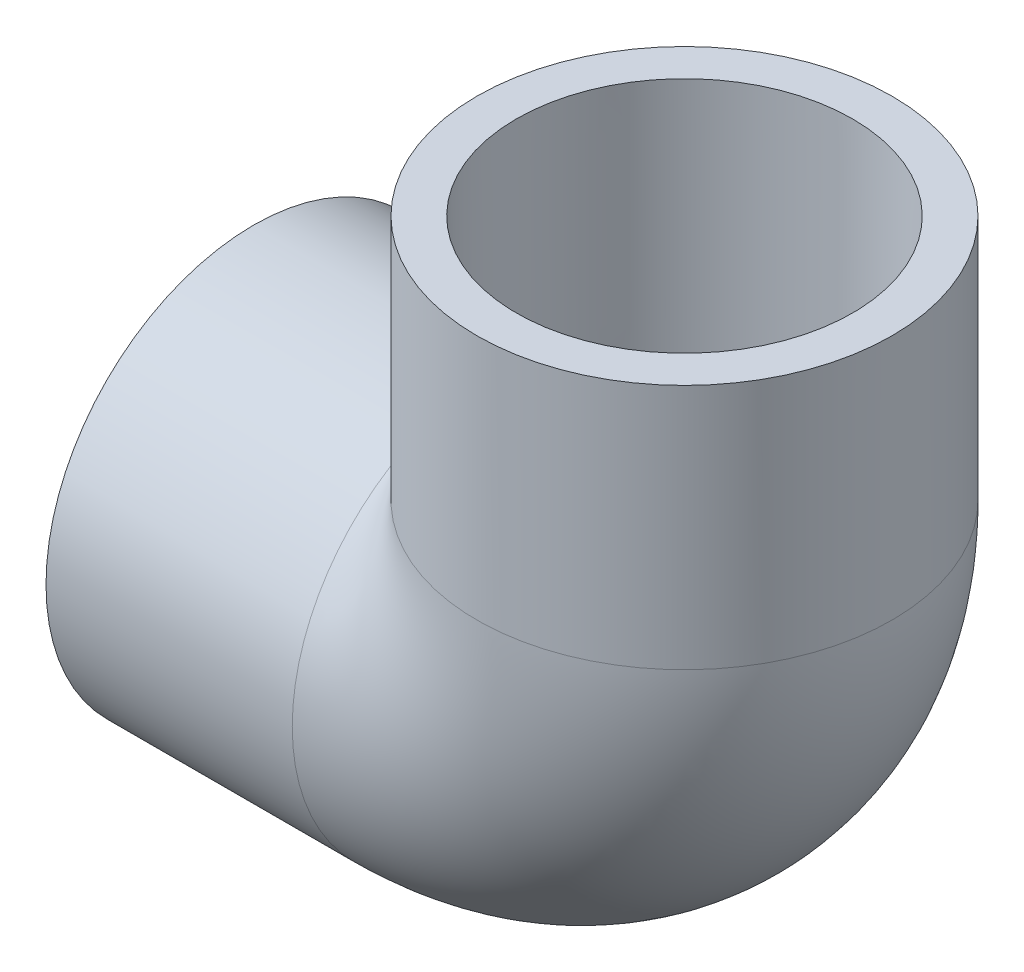
SolidWorks part; units mm, degrees
ref_plane "Front Plane" through (0, 0, 0) normal (0, 0, 1) x (1, 0, 0)
ref_plane "Top Plane" through (0, 0, 0) normal (0, 1, 0) x (1, 0, 0)
ref_plane "Right Plane" through (0, 0, 0) normal (1, 0, 0) x (0, 0, -1)
sketch "Sketch0" plane through (0, 0, 0) normal (0, 0, 1) x (1, 0, 0)
  line L0 (-62.23, 0) -> (0, 0) construction
  line L1 (0, 0) -> (0, 62.23) construction
  line L2 (-26.67, 0) -> (0, 0) construction
  line L3 (0, 0) -> (0, 26.67) construction
  line L4 (-62.23, 29.972) -> (-62.23, -29.972) construction
  line L5 (-26.67, 24.0538) -> (-62.23, 24.2824) construction
  line L6 (-26.67, 24.0538) -> (-26.67, -24.0538) construction
  line L7 (-26.67, -24.0538) -> (-62.23, -24.2824) construction
  line L8 (-62.23, 24.2824) -> (-62.23, -24.2824) construction
  line L9 (-29.972, 62.23) -> (29.972, 62.23) construction
  line L10 (-24.2824, 62.23) -> (24.2824, 62.23) construction
  line L11 (24.2824, 62.23) -> (24.0538, 26.67) construction
  line L12 (24.0538, 26.67) -> (-24.0538, 26.67) construction
  line L13 (-24.0538, 26.67) -> (-24.2824, 62.23) construction
  line L14 (-26.67, 19.05) -> (-26.67, -19.05) construction
  line L18 (-19.05, 26.67) -> (19.05, 26.67) construction
  dimension "H" = 62.23
  dimension "G" = 26.67
  dimension "M" = 59.944
  dimension "OD A" = 48.5648
  dimension "OD B" = 48.1076
  dimension "ID" = 38.1
sketch "Sketch1" plane through (0, 0, 0) normal (0, 0, 1) x (1, 0, 0)
  line L0 (-62.23, 0) -> (0, 0) construction
  line L1 (-62.23, 0) -> (0, 0) construction
  line L3 (-62.23, -29.972) -> (-26.67, -29.972)
  line L4 (-62.23, -29.972) -> (-62.23, -24.2824)
  line L5 (-62.23, -24.2824) -> (-26.67, -24.0538)
  line L6 (-26.67, -29.972) -> (-26.67, -24.0538)
revolve "Revolve1" add sketch "Sketch1" angle 360 about L1
sketch "Sketch2" plane through (0, 0, 0) normal (0, 0, 1) x (1, 0, 0)
  line L0 (24.2824, 62.23) -> (24.0538, 26.67)
  line L1 (24.0538, 26.67) -> (29.972, 26.67)
  line L2 (29.972, 26.67) -> (29.972, 62.23)
  line L3 (29.972, 62.23) -> (24.2824, 62.23)
  line L4 (0, 0) -> (0, 62.23) construction
  line L5 (0, 0) -> (0, 62.23) construction
revolve "Revolve2" add sketch "Sketch2" angle 360 about L5
sketch "Sketch3" plane through (-26.67, 0, 0) normal (1, 0, 0) x (0, 0, -1)
  circle A0 centre (0, 0) radius 19.05
  circle A1 centre (0, 0) radius 29.972
sketch "Sketch4" plane through (0, 0, 0) normal (0, 0, 1) x (1, 0, 0)
  line L0 (-62.23, 0) -> (0, 0) construction
  line L1 (0, 0) -> (0, 62.23) construction
  line L2 (-62.23, 0) -> (-26.67, 0) construction
  line L3 (0, 26.67) -> (0, 62.23) construction
  arc A0 (-26.67, 0) -> (0, 26.67) centre (-26.67, 26.67) ccw
sweep "Sweep1" add profiles "Sketch3" path "Sketch4"
other "CPoint1" parameters "Diameter"=38.1, "StubLength"=57.15
ref_axis "Axis1" through (-36.67, 0, 0) along (1, 0, 0)
other "CPoint2" parameters "Diameter"=38.1, "StubLength"=57.15
ref_axis "Axis2" through (0, 36.67, 0) along (0, -1, 0)
other "RPoint1"
scale "Scale1" bodies to scale 104 scale about origin uniform scaling yes scale factor 0.865
